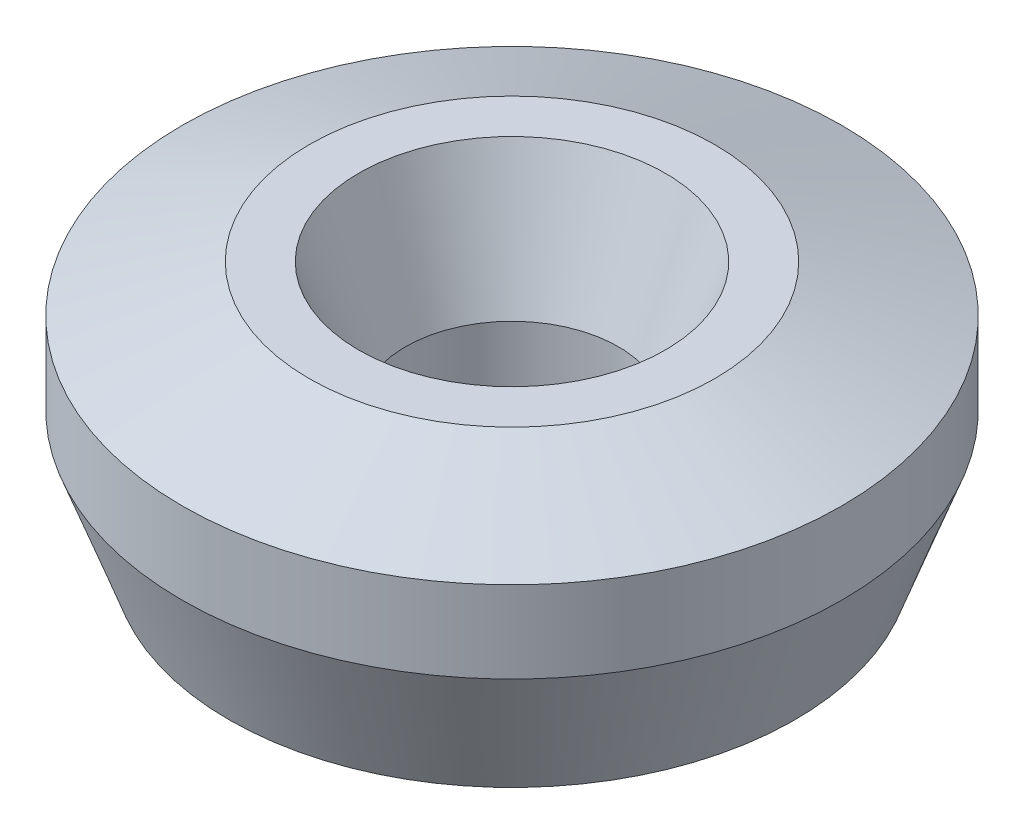
SolidWorks part; units mm, degrees
ref_plane "Front Plane" through (0, 0, 0) normal (0, 0, 1) x (1, 0, 0)
ref_plane "Top Plane" through (0, 0, 0) normal (0, 1, 0) x (1, 0, 0)
ref_plane "Right Plane" through (0, 0, 0) normal (1, 0, 0) x (0, 0, -1)
sketch "Sketch1" plane through (0, 0, 0) normal (0, 1, 0) x (1, 0, 0)
  circle A0 centre (0, 0) radius 10
  dimension "SLEEVE_OD" = 20
extrude "Boss-Extrude1" add sketch "Sketch1" along normal blind 7.7454
sketch "Sketch2" plane through (0, 0, 0) normal (0, 1, 0) x (1, 0, 0)
  circle A0 centre (0, 0) radius 3.2303
  dimension "BORE_D" = 6.4606
extrude "Cut-Extrude1" cut sketch "Sketch2" along normal through all
chamfer "Chamfer1" distance 1.4184 angle 69.777 4 edges at (0, 7.7454, 3.2303) (0, 0, 3.2303) (0, 0, 10) (0, 7.7454, 10) first distance on face at (0, 7.7454, 3.2303) first distance on face at (0, 0, 3.2303) first distance on face at (0, 7.7454, 10)
